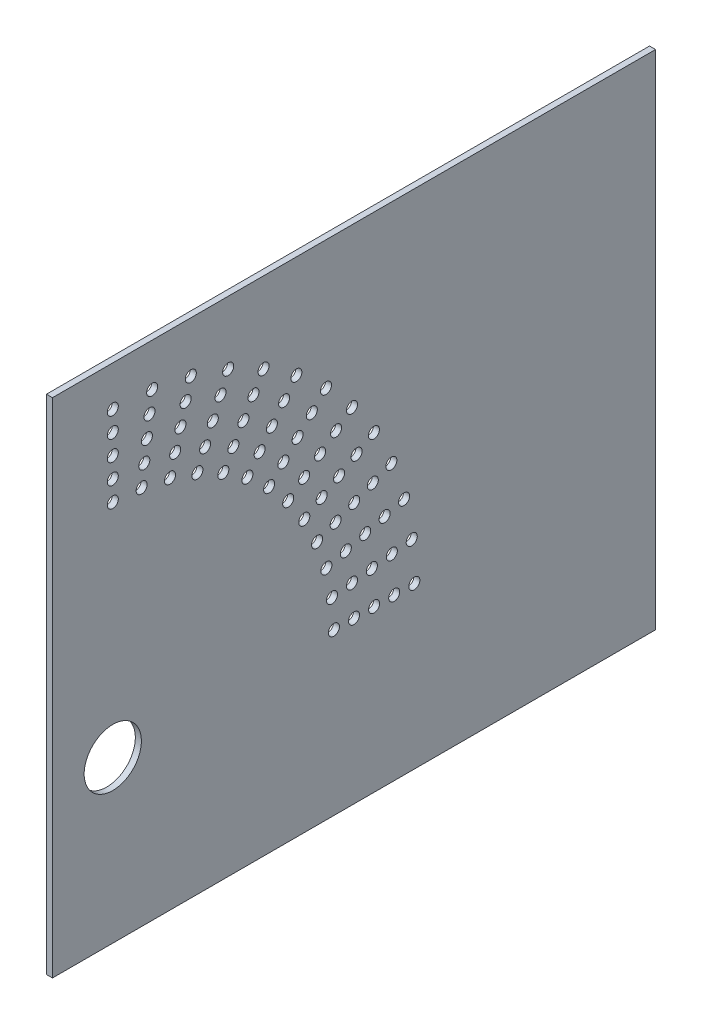
SolidWorks part; units mm, degrees
ref_plane "Front Plane" through (0, 0, 0) normal (0, 0, 1) x (1, 0, 0)
ref_plane "Top Plane" through (0, 0, 0) normal (0, 1, 0) x (1, 0, 0)
ref_plane "Right Plane" through (0, 0, 0) normal (1, 0, 0) x (0, 0, -1)
sketch "Sketch1" plane through (0, 0, 0) normal (1, 0, 0) x (0, 0, -1)
  line L1 (0, 0) -> (300, 0)
  line L2 (0, 0) -> (0, 250)
  line L3 (0, 250) -> (300, 250)
  line L4 (300, 0) -> (300, 250)
  circle A0 centre (30, 80) radius 14.235
  dimension "D1" = 300
  dimension "D5" = 28.47
  dimension "D4" = 170
  dimension "D2" = 250
  dimension "D3" = 30
extrude "Boss-Extrude1" add sketch "Sketch1" along normal blind 3
sketch "Sketch2" plane through (3, 0, 0) normal (1, 0, 0) x (0, 0, -1)
  line L0 (30, 191.2804) -> (30, 238.9618)
  line L5 (30, 238.9618) -> (249.7561, 238.9618)
  line L6 (249.7561, 238.9618) -> (249.7561, 80)
  line L7 (249.7561, 80) -> (141.2804, 80)
  arc A0 (141.2804, 80) -> (30, 191.2804) centre (30, 80) ccw
sketch "Sketch3" plane through (3, 0, 0) normal (1, 0, 0) x (0, 0, -1)
  line L0 (30, 230) -> (30, 80) construction
  circle A0 centre (30, 230) radius 2.75
  circle A1 centre (30, 220) radius 2.75
  circle A2 centre (30, 210) radius 2.75
  circle A3 centre (30, 200) radius 2.75
  circle A4 centre (30, 190) radius 2.75
  dimension "D1" = 5.5
  dimension "D3" = 10
  dimension "D2" = 150
  dimension "D4" = 10
  dimension "D5" = 10
  dimension "D6" = 10
extrude "Cut-Extrude2" cut sketch "Sketch3" against normal blind 3 contours A0 | A1 | A2 | A3 | A4
pattern_circular "CirPattern1" count 13 over 90 about axis through (3, 80, -30) along (1, 0, 0) of "Cut-Extrude2" reverse direction yes
sketch "Sketch4" plane through (3, 0, 0) normal (1, 0, 0) x (0, 0, -1)
  line L0 (140, 80) -> (140.2627, 70) construction
  circle A0 centre (140.2627, 70) radius 2.75
  circle A1 centre (147.44, 70) radius 2.75
  circle A2 centre (157.692, 70) radius 2.75
  circle A3 centre (168.9062, 70) radius 2.75
  circle A4 centre (180.2649, 70) radius 2.75
  point P12 (0, 0)
  dimension "D1" = 5.5
  dimension "D2" = 5.5
  dimension "D3" = 5.5
  dimension "D4" = 5.5
  dimension "D5" = 5.5
  dimension "D6" = 10
